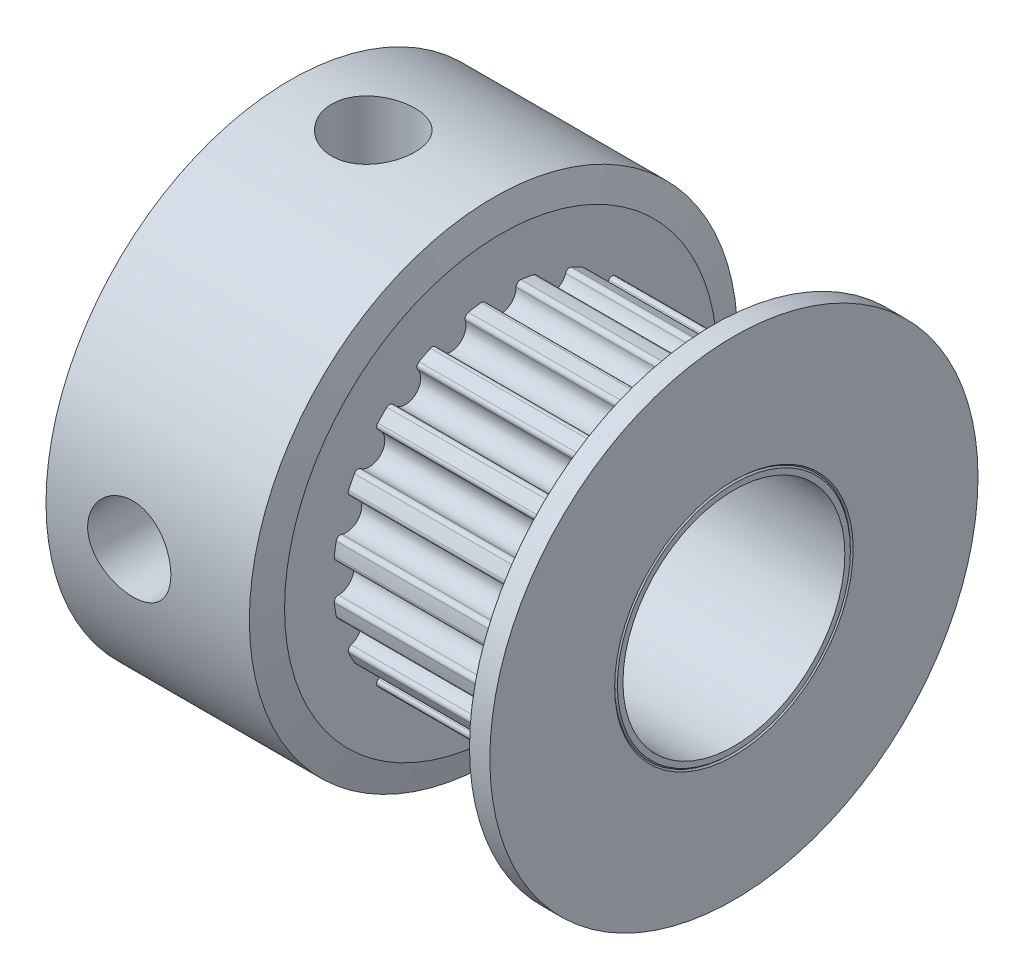
SolidWorks part; units mm, degrees
material "6063-T1"
ref_plane "Front Plane" through (0, 0, 0) normal (0, 0, 1) x (1, 0, 0)
ref_plane "Top Plane" through (0, 0, 0) normal (0, 1, 0) x (1, 0, 0)
ref_plane "Right Plane" through (0, 0, 0) normal (1, 0, 0) x (0, 0, -1)
sketch "Sketch1" plane through (0, 0, 0) normal (0, 0, 1) x (1, 0, 0)
  line L0 (0, 0) -> (0, 8.8)
  line L1 (0, 8.8) -> (6.6, 8.8)
  line L2 (6.6, 8.8) -> (7.3321, 8.8)
  line L3 (7.3321, 8.8) -> (7.6, 7.8)
  line L4 (7.6, 6.05) -> (15, 6.05)
  line L5 (15, 6.05) -> (15, 7.8)
  line L6 (15.2679, 8.8) -> (16, 8.8)
  line L7 (16, 0) -> (16, 4.2)
  line L8 (16, 4.3) -> (15.95, 4.25)
  line L9 (15.95, 4.25) -> (16, 4.2)
  line L10 (16, 4.3) -> (16, 8.8)
  line L11 (0, 0) -> (16, 0)
  line L12 (7.6, 7.8) -> (7.6, 6.05)
  line L13 (15, 7.8) -> (15.2679, 8.8)
  line L14 (0, 0) -> (-50000, 0) construction
  dimension "D2" = 0.05
  dimension "D3" = 15
  dimension "D4" = 4.25
  dimension "D5" = 1
  dimension "D6" = 6.05
  dimension "D7" = 17.6
  dimension "D9" = 1
  dimension "D10" = 9.4
revolve "Body" add sketch "Sketch1" angle 360 about L11 region at (7.4337, 3.8787, 0)
sketch "Sketch 2" plane through (16, 0, 0) normal (1, 0, 0) x (0, 0, -1)
  circle A0 centre (0, 0) radius 4
  dimension "D1" = 8
extrude "Bore" cut sketch "Sketch 2" against normal through all
sketch "Sketch 3" plane through (7.6, 0, 0) normal (1, 0, 0) x (0, 0, -1)
  line L0 (0, 0) -> (9.7637, 0) construction
  circle A0 centre (5.5684, -1.8093) radius 0.55
  circle A2 centre (4.7368, -3.4415) radius 0.55
  circle A3 centre (3.4415, -4.7368) radius 0.55
  circle A4 centre (1.8093, -5.5684) radius 0.55
  circle A5 centre (0, -5.855) radius 0.55
  circle A6 centre (5.855, 0) radius 0.55
  circle A7 centre (-1.8093, -5.5684) radius 0.55
  circle A8 centre (-3.4415, -4.7368) radius 0.55
  circle A9 centre (-4.7368, -3.4415) radius 0.55
  circle A10 centre (-5.5684, -1.8093) radius 0.55
  circle A11 centre (-5.855, 0) radius 0.55
  circle A12 centre (-5.5684, 1.8093) radius 0.55
  circle A13 centre (-4.7368, 3.4415) radius 0.55
  circle A14 centre (-3.4415, 4.7368) radius 0.55
  circle A17 centre (-1.8093, 5.5684) radius 0.55
  circle A18 centre (0, 5.855) radius 0.55
  circle A19 centre (1.8093, 5.5684) radius 0.55
  circle A20 centre (3.4415, 4.7368) radius 0.55
  circle A21 centre (4.7368, 3.4415) radius 0.55
  circle A22 centre (5.5684, 1.8093) radius 0.55
  point P45 (0, 0)
  dimension "D1" = 5.855
extrude "20tooth" cut sketch "Sketch 3" along normal up to surface (7.4 mm away) up to face at (15, 0, 7.8)
fillet "Filets" radius 0.15 40 edges at (11.3, -0.5223, -6.0274) (11.3, 0.5223, -6.0274) (11.3, -1.3659, -5.8938) (11.3, -2.3593, -5.571) (11.3, -3.1203, -5.1833) (11.3, -3.9654, -4.5693) (11.3, -4.5693, -3.9654) (11.3, -5.1833, -3.1203) (11.3, -5.571, -2.3593) (11.3, -5.8938, -1.3659) (11.3, -6.0274, -0.5223) (11.3, -6.0274, 0.5223) (11.3, -5.8938, 1.3659) (11.3, -5.571, 2.3593) (11.3, -5.1833, 3.1203) (11.3, -4.5693, 3.9654) (11.3, -3.9654, 4.5693) (11.3, -3.1203, 5.1833) (11.3, -2.3593, 5.571) (11.3, -1.3659, 5.8938) (11.3, -0.5223, 6.0274) (11.3, 0.5223, 6.0274) (11.3, 1.3659, 5.8938) (11.3, 2.3593, 5.571) (11.3, 3.1203, 5.1833) (11.3, 3.9654, 4.5693) (11.3, 4.5693, 3.9654) (11.3, 5.1833, 3.1203) (11.3, 5.571, 2.3593) (11.3, 5.8938, 1.3659) (11.3, 6.0274, -0.5223) (11.3, 5.571, -2.3593) (11.3, 4.5693, -3.9654) (11.3, 3.1203, -5.1833) (11.3, 1.3659, -5.8938) (11.3, 2.3593, -5.571) (11.3, 3.9654, -4.5693) (11.3, 6.0274, 0.5223) (11.3, 5.8938, -1.3659) (11.3, 5.1833, -3.1203)
sketch "Sketch 4" plane through (0, 0, 0) normal (0, 0, 1) x (1, 0, 0)
  circle A0 centre (3, 0) radius 1.5
  dimension "D1" = 3
  dimension "D2" = 3
extrude "Set screw" cut sketch "Sketch 4" along normal through all
ref_axis "Axis 1" through (0, 0, 0) along (1, 0, 0)
pattern_circular "Set screw pattern" count 2 over 270 about axis through (0, 0, 0) along (1, 0, 0) of "Set screw"
sketch "Sketch2" plane through (7.6, 0, 0) normal (1, 0, 0) x (0, 0, -1)
  circle A0 centre (0, 0) radius 5.725
  circle A2 centre (0, 0) radius 7.025
  dimension "D1" = 11.45
  dimension "D3" = 14.05
